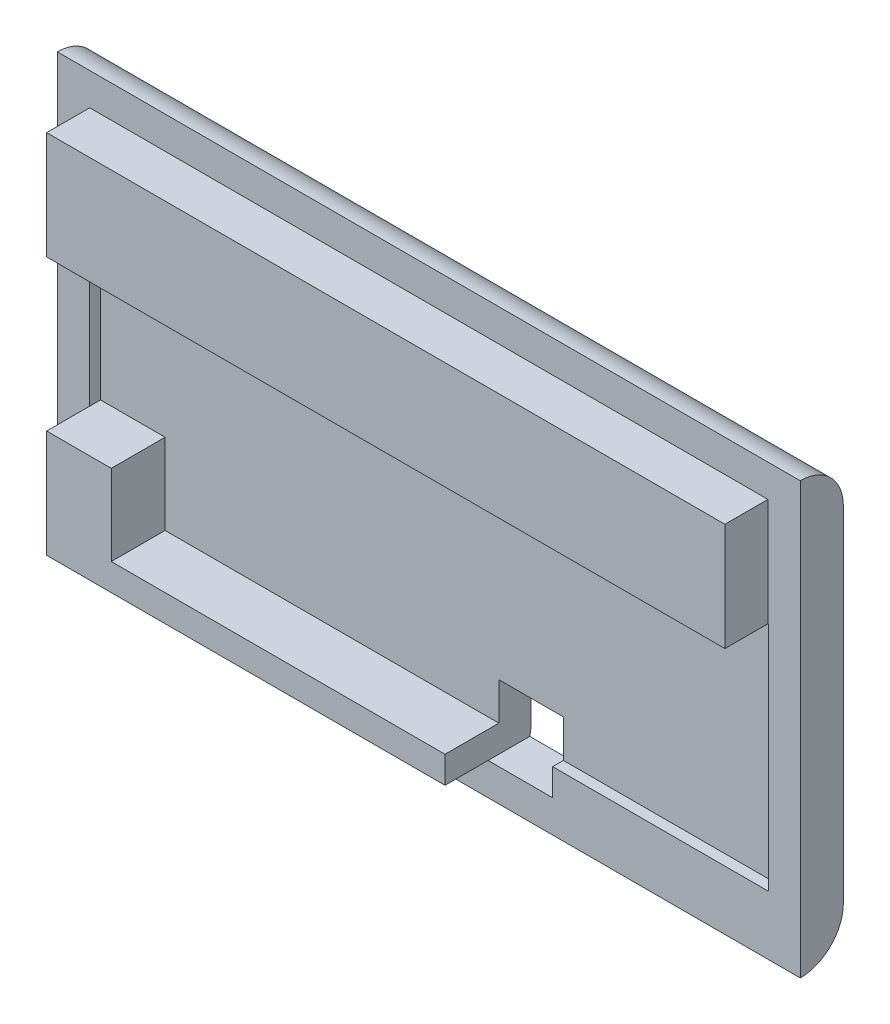
SolidWorks part; units mm, degrees
ref_plane "Ebene vorne" through (0, 0, 0) normal (0, 0, 1) x (1, 0, 0)
ref_plane "Ebene oben" through (0, 0, 0) normal (0, 1, 0) x (1, 0, 0)
ref_plane "Ebene rechts" through (0, 0, 0) normal (1, 0, 0) x (0, 0, -1)
sketch "Sketch1" plane through (0, 0, 0) normal (0, 0, 1) x (1, 0, 0)
  line L1 (-17.25, 10) -> (17.25, 10)
  line L2 (-17.25, 10) -> (-17.25, -10)
  line L3 (-17.25, -10) -> (17.25, -10)
  line L4 (17.25, 10) -> (17.25, -10)
  line L5 (-17.25, 10) -> (17.25, -10) construction
  line L6 (-17.25, -10) -> (17.25, 10) construction
  point P0 (0, 0)
  dimension "D1" = 34.5
  dimension "D2" = 20
extrude "Boss-Extrude1" add sketch "Sketch1" along normal blind 2
sketch "Sketch2" plane through (0, 0, 2) normal (0, 0, 1) x (1, 0, 0)
  line L2 (-17.25, 10) -> (-17.25, -10) construction
  line L3 (-17.25, -10) -> (17.25, -10) construction
  line L4 (17.25, 10) -> (17.25, -10) construction
  line L5 (-17.25, 10) -> (17.25, 10) construction
  line L14 (17.25, 10) -> (-17.25, 10) construction
  line L15 (-17.25, 10) -> (17.25, 10) construction
  line L16 (-17.25, 10) -> (-17.25, 2) construction
  line L18 (-17.25, 2) -> (17.25, 2) construction
  line L19 (17.25, 10) -> (17.25, 2) construction
  line L20 (-15.75, 8.5) -> (-15.75, 3.5)
  line L21 (-15.75, 3.5) -> (15.75, 3.5)
  line L22 (15.75, 8.5) -> (15.75, 3.5)
  line L23 (-15.75, 8.5) -> (15.75, 8.5)
  line L24 (1.1, 0) -> (-1.1, 0) construction
  line L25 (-15.75, -8.5) -> (15.75, -8.5)
  line L26 (15.75, -8.5) -> (15.75, -3.5)
  line L27 (-15.75, -3.5) -> (15.75, -3.5)
  line L28 (-15.75, -8.5) -> (-15.75, -3.5)
  point P0 (0, 0)
  point P7 (-15.25, 8)
  point P8 (-15.25, -8)
  point P9 (15.25, -8)
  point P10 (15.25, 8)
  dimension "D2" = 0
  dimension "D3" = 1.5
  dimension "D1" = 5
extrude "Boss-Extrude2" add sketch "Sketch2" along normal blind 2
sketch "Sketch3" plane through (0, 0, 0) normal (0, 0, -1) x (-1, 0, 0)
  line L0 (15.75, -8.5) -> (-15.75, -8.5) construction
  line L1 (-2.75, -8.5) -> (-5.75, -8.5)
  line L2 (-2.75, -8.5) -> (-2.75, -5.5)
  line L4 (-5.75, -8.5) -> (-5.75, -5.5)
  line L6 (-5.75, -5.5) -> (-2.75, -5.5)
  line L7 (-15.75, -8.5) -> (-15.75, -3.5) construction
  dimension "D1" = 10
  dimension "D3" = 3
extrude "Cut-Extrude1" cut sketch "Sketch3" against normal blind 10
fillet "Fillet1" radius 2 2 edges at (0, -10, 0) (0, 10, 0)
sketch "Sketch4" plane through (0, 0, 4) normal (0, 0, 1) x (1, 0, 0)
  line L0 (15.75, -3.5) -> (-15.75, -3.5) construction
  line L1 (15.75, -8.5) -> (5.75, -8.5)
  line L2 (15.75, -8.5) -> (15.75, -3.5)
  line L3 (15.75, -3.5) -> (5.75, -3.5)
  line L4 (5.75, -8.5) -> (5.75, -5.5)
  line L5 (5.75, -5.5) -> (5.75, -8.5) construction
  line L6 (15.75, -3.5) -> (-15.75, -3.5) construction
  line L7 (-12.75, -3.5) -> (5.75, -3.5)
  line L8 (-12.75, -3.5) -> (-12.75, -5.5)
  line L9 (-12.75, -5.5) -> (5.75, -5.5)
  line L11 (-15.75, -3.5) -> (-15.75, -8.5) construction
  dimension "D1" = 2
  dimension "D2" = 3
extrude "Cut-Extrude2" cut sketch "Sketch4" against normal blind 2
sketch "Sketch6" plane through (0, 0, 4) normal (0, 0, 1) x (1, 0, 0)
  line L0 (2.75, -5.5) -> (5.75, -5.5) construction
  line L1 (-15.75, 3.5) -> (15.7629, 3.5)
  line L2 (-15.75, 3.5) -> (-15.75, -3.5)
  line L3 (-12.75, -7.25) -> (15.7629, -7.25)
  line L4 (15.7629, 3.5) -> (15.7629, -7.25)
  line L5 (-12.75, -3.5) -> (-12.75, -5.5) construction
  line L6 (-15.75, -3.5) -> (-12.75, -3.5)
  line L9 (-12.75, -3.5) -> (-12.75, -7.25)
  dimension "D1" = 1.75
extrude "Cut-Extrude3" cut sketch "Sketch6" against normal blind 2.5
